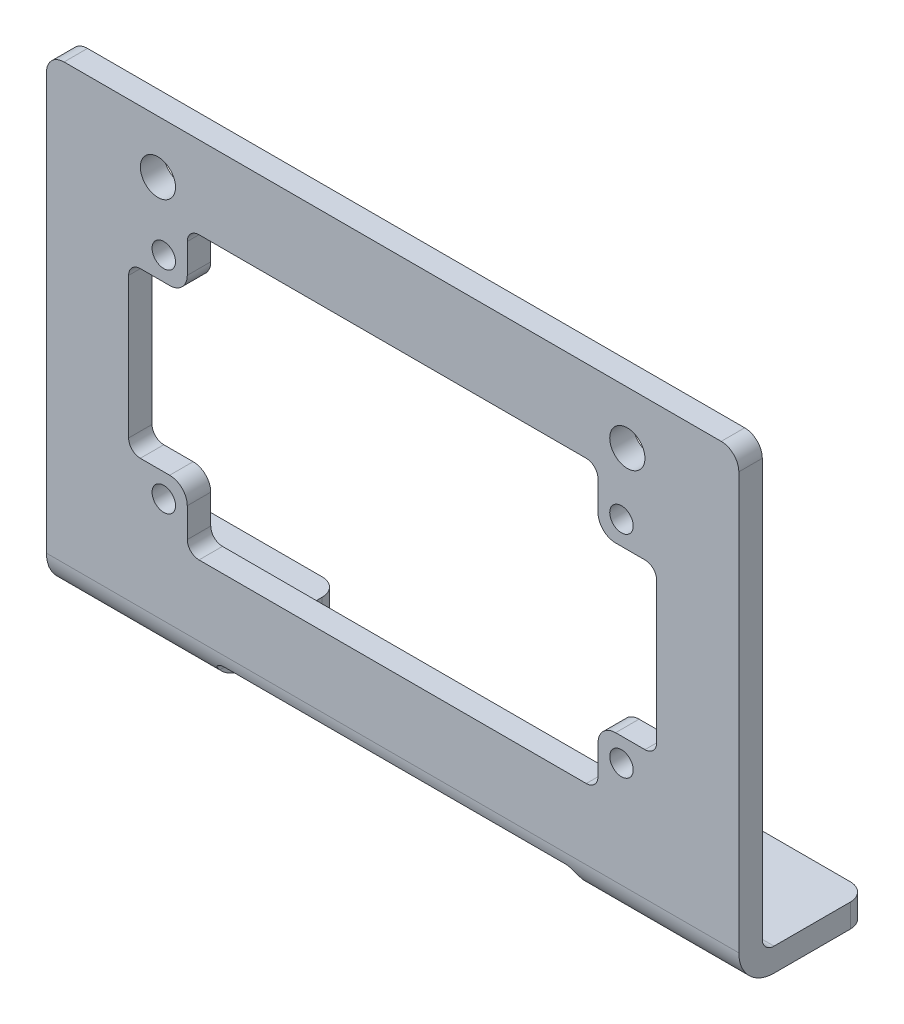
SolidWorks part; units mm, degrees
ref_plane "Front Plane" through (0, 0, 0) normal (0, 0, 1) x (1, 0, 0)
ref_plane "Top Plane" through (0, 0, 0) normal (0, 1, 0) x (1, 0, 0)
ref_plane "Right Plane" through (0, 0, 0) normal (1, 0, 0) x (0, 0, -1)
sketch "Sketch1" plane through (0, 0, 0) normal (0, 0, 1) x (1, 0, 0)
  line L0 (0, -55) -> (0, 55) construction
  line L1 (29.5, -20) -> (-29.5, -20) construction
  line L2 (29.5, -20) -> (29.5, 20) construction
  line L3 (29.5, 20) -> (-29.5, 20) construction
  line L4 (-29.5, -20) -> (-29.5, 20) construction
  line L5 (29.5, -20) -> (-29.5, 20) construction
  line L6 (29.5, 20) -> (-29.5, -20) construction
  line L11 (15.5, -18) -> (-15.5, -18) construction
  line L12 (15.5, -18) -> (15.5, -20) construction
  line L13 (15.5, -20) -> (-15.5, -20) construction
  line L14 (-15.5, -18) -> (-15.5, -20) construction
  line L15 (15.5, -18) -> (-15.5, -20) construction
  line L16 (15.5, -20) -> (-15.5, -18) construction
  line L17 (-22.5, 8) -> (-17.5, 8)
  line L18 (22.5, 13) -> (-22.5, 13) construction
  line L19 (22.5, 13) -> (22.5, -11) construction
  line L20 (22.5, -11) -> (-22.5, -11) construction
  line L21 (-22.5, 13) -> (-22.5, -11) construction
  line L22 (22.5, 13) -> (-22.5, -11) construction
  line L23 (22.5, -11) -> (-22.5, 13) construction
  line L24 (-17.5, 8) -> (-17.5, 13)
  line L25 (-5.0155, 1) -> (4.7745, 1) construction
  line L26 (-22.5, -6) -> (-17.5, -6)
  line L27 (-17.5, -6) -> (-17.5, -11)
  line L28 (-17.5, 13) -> (17.5, 13)
  line L29 (-22.5, 8) -> (-22.5, -6)
  line L30 (-17.5, -11) -> (17.5, -11)
  line L31 (-15.5, -18) -> (15.5, -18)
  line L32 (-15.5, -20) -> (-29.5, -20)
  line L33 (-29.5, -20) -> (-29.5, 20)
  line L34 (-29.5, 20) -> (29.5, 20)
  line L35 (-15.5, -18) -> (-15.5, -20)
  line L36 (5.0155, 1) -> (-4.7745, 1) construction
  line L37 (-22.5, -11) -> (22.5, 13) construction
  line L38 (-22.5, 13) -> (22.5, -11) construction
  line L39 (22.5, 13) -> (22.5, -11) construction
  line L40 (-15.5, -20) -> (15.5, -18) construction
  line L41 (-15.5, -18) -> (15.5, -20) construction
  line L42 (15.5, -18) -> (15.5, -20) construction
  line L43 (-29.5, 20) -> (29.5, -20) construction
  line L44 (-29.5, -20) -> (29.5, 20) construction
  line L45 (29.5, -20) -> (29.5, 20) construction
  line L46 (15.5, -18) -> (15.5, -20)
  line L47 (29.5, -20) -> (29.5, 20)
  line L48 (15.5, -20) -> (29.5, -20)
  line L49 (22.5, 8) -> (22.5, -6)
  line L50 (17.5, -6) -> (17.5, -11)
  line L51 (22.5, -6) -> (17.5, -6)
  line L52 (17.5, 8) -> (17.5, 13)
  line L53 (22.5, 8) -> (17.5, 8)
  circle A0 centre (-19.5, 10) radius 1
  circle A1 centre (-20, 15.5) radius 1.5
  circle A2 centre (-19.5, -8) radius 1
  circle A3 centre (19.5, -8) radius 1
  circle A4 centre (20, 15.5) radius 1.5
  circle A5 centre (19.5, 10) radius 1
  point P0 (0, 0)
  point P7 (0, -19)
  point P15 (0, 1)
  point P36 (0, -18)
  point P44 (0, 20)
  point P45 (0, -11)
  point P48 (0, 13)
  point P50 (0, 1)
  dimension "D12" = 2
  dimension "D14" = 3
  dimension "D1" = 40
  dimension "D2" = 59
  dimension "D3" = 31
  dimension "D4" = 2
  dimension "D5" = 7
  dimension "D6" = 7
  dimension "D7" = 7
  dimension "D8" = 5
  dimension "D9" = 5
  dimension "D10" = 10
  dimension "D11" = 10
  dimension "D13" = 9.5
  dimension "D15" = 4.5
extrude "Boss-Extrude1" add sketch "Sketch1" along normal blind 2
sketch "Sketch4" plane through (0, -20, 0) normal (0, -1, 0) x (1, 0, 0)
  line L0 (-15.5, 2) -> (-15.5, 0) construction
  line L1 (-29.5, 2) -> (-15.5, 2) construction
  line L2 (-29.5, 2) -> (-29.5, 0) construction
  line L3 (-15.5, 2) -> (-15.5, 0)
  line L4 (-29.5, 2) -> (-15.5, 2)
  line L5 (-29.5, 2) -> (-29.5, 0)
  line L6 (-29.5, 0) -> (-29.5, -9)
  line L7 (-29.5, -9) -> (-15.5, -9)
  line L8 (-15.5, -9) -> (-15.5, 0)
  line L9 (0, -55) -> (0, 55) construction
  line L10 (15.5, -9) -> (15.5, 0)
  line L11 (29.5, -9) -> (15.5, -9)
  line L12 (29.5, 0) -> (29.5, -9)
  line L13 (29.5, 2) -> (29.5, 0)
  line L14 (29.5, 2) -> (15.5, 2)
  line L15 (15.5, 2) -> (15.5, 0)
  circle A0 centre (-20, -4) radius 1.5
  circle A1 centre (20, -4) radius 1.5
  dimension "D4" = 3
  dimension "D1" = 11
  dimension "D2" = 4.5
  dimension "D3" = 5
extrude "Boss-Extrude2" add sketch "Sketch4" against normal up to surface (2 mm away) up to face at (0, -18, 1)
fillet "Fillet2" radius 1.5 10 edges at (-29.5, -19, -9) (15.5, -19, -9) (-15.5, -19, -9) (29.5, -19, -9) (17.5, -6, 1) (-17.5, -6, 1) (-17.5, 8, 1) (17.5, 8, 1) (-29.5, 20, 1) (29.5, 20, 1)
fillet "Fillet3" radius 1 10 edges at (15.5, -18, 1) (-15.5, -18, 1) (-22.5, 8, 1) (-17.5, 13, 1) (-22.5, -6, 1) (-17.5, -11, 1) (17.5, -11, 1) (17.5, 13, 1) (22.5, 8, 1) (22.5, -6, 1)
fillet "Fillet4" radius 1 2 edges at (-22.5, -18, 0) (22.5, -18, 0)
fillet "Fillet5" radius 3 1 edges at (22.5, -20, 2)
